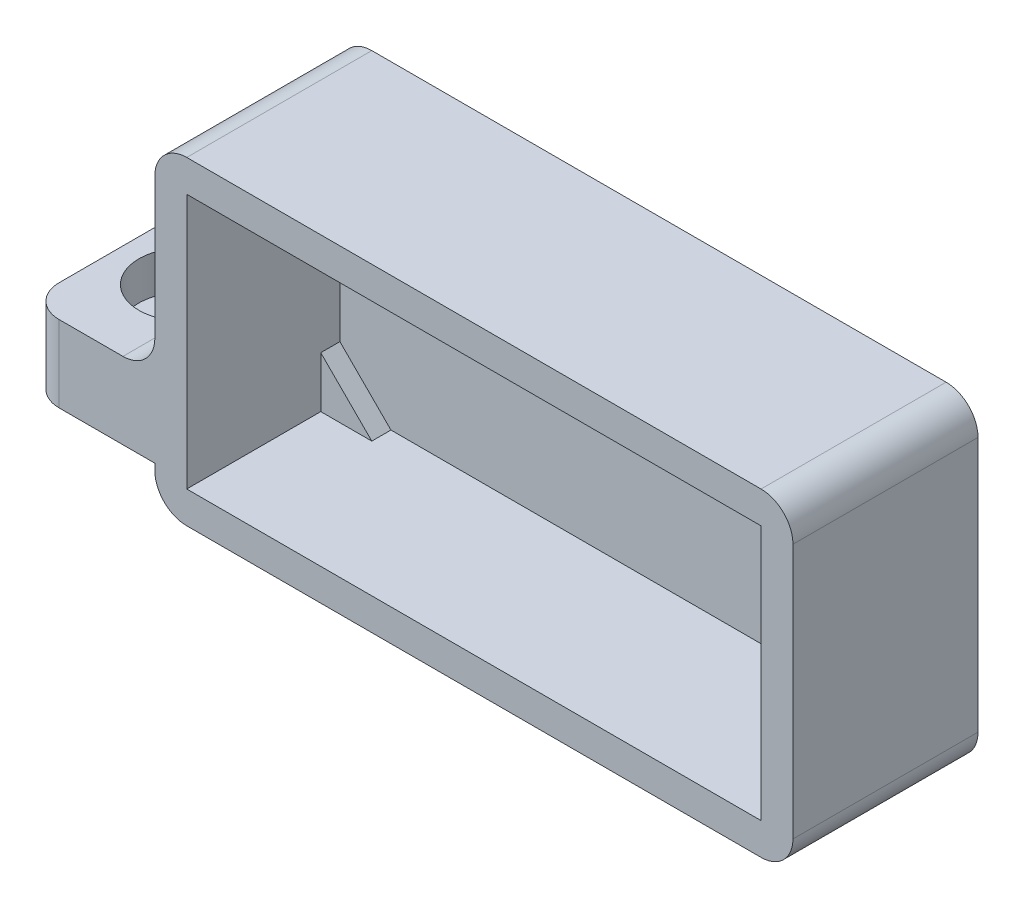
SolidWorks part; units mm, degrees
ref_plane "Front Plane" through (0, 0, 0) normal (0, 0, 1) x (1, 0, 0)
ref_plane "Top Plane" through (0, 0, 0) normal (0, 1, 0) x (1, 0, 0)
ref_plane "Right Plane" through (0, 0, 0) normal (1, 0, 0) x (0, 0, -1)
sketch "Sketch1" plane through (0, 0, 0) normal (0, 0, 1) x (1, 0, 0)
  line L1 (-25, 12.5) -> (25, 12.5)
  line L2 (-25, 12.5) -> (-25, -12.5)
  line L3 (-25, -12.5) -> (25, -12.5)
  line L4 (25, 12.5) -> (25, -12.5)
  line L5 (-25, 12.5) -> (25, -12.5) construction
  line L6 (-25, -12.5) -> (25, 12.5) construction
  point P0 (0, 0)
  dimension "D1" = 25
  dimension "D2" = 50
extrude "Boss-Extrude1" add sketch "Sketch1" along normal blind 2.5
sketch "Sketch2" plane through (0, 0, 2.5) normal (0, 0, 1) x (1, 0, 0)
  line L0 (25, 12.5) -> (-25, 12.5) construction
  line L1 (-22.5, 10) -> (22.5, 10)
  line L2 (-22.5, 10) -> (-22.5, -10)
  line L3 (-22.5, -10) -> (22.5, -10)
  line L4 (22.5, 10) -> (22.5, -10)
  line L5 (-22.5, 10) -> (22.5, -10) construction
  line L6 (-22.5, -10) -> (22.5, 10) construction
  line L7 (-25, 12.5) -> (-25, -12.5) construction
  line L9 (25, 12.5) -> (-25, 12.5)
  line L10 (25, 12.5) -> (25, -12.5)
  line L11 (25, -12.5) -> (-25, -12.5)
  line L12 (-25, 12.5) -> (-25, -12.5)
  line L13 (25, 12.5) -> (-25, -12.5) construction
  line L14 (25, -12.5) -> (-25, 12.5) construction
  point P0 (0, 0)
  point P10 (0, 0)
  dimension "D1" = 2.5
  dimension "D2" = 2.5
extrude "Boss-Extrude2" add sketch "Sketch2" along normal blind 12
sketch "Sketch4" plane through (0, 0, 2.5) normal (0, 0, 1) x (1, 0, 0)
  line L0 (0, 10) -> (0, -10) construction
  line L1 (22.5, 10) -> (-22.5, 10) construction
  line L2 (-22.5, -10) -> (22.5, -10) construction
  line L3 (-22.5, 0) -> (22.5, 0) construction
  line L4 (-22.5, 10) -> (-22.5, -10) construction
  line L5 (22.5, -10) -> (22.5, 10) construction
  line L6 (-22.5, 10) -> (-22.5, 6)
  line L7 (-22.5, 6) -> (-18.5, 10)
  line L8 (22.5, 10) -> (-22.5, 10) construction
  line L9 (-18.5, 10) -> (-22.5, 10)
  line L10 (18.5, 10) -> (22.5, 10)
  line L11 (22.5, 6) -> (18.5, 10)
  line L12 (22.5, 10) -> (22.5, 6)
  line L13 (22.5, -10) -> (22.5, -6)
  line L14 (22.5, -6) -> (18.5, -10)
  line L15 (18.5, -10) -> (22.5, -10)
  line L16 (-18.5, -10) -> (-22.5, -10)
  line L17 (-22.5, -6) -> (-18.5, -10)
  line L18 (-22.5, -10) -> (-22.5, -6)
  dimension "D1" = 4
extrude "Boss-Extrude3" add sketch "Sketch4" along normal blind 1.5
sketch "Sketch5" plane through (-25, 0, 0) normal (-1, 0, 0) x (0, 0, 1)
  line L0 (0, 12.5) -> (0, -12.5) construction
  line L1 (0, -3.5) -> (14.5, -3.5)
  line L2 (0, -3.5) -> (0, -9.5)
  line L3 (0, -9.5) -> (14.5, -9.5)
  line L4 (14.5, -3.5) -> (14.5, -9.5)
  line L5 (14.5, 12.5) -> (14.5, -12.5) construction
  line L6 (14.5, -12.5) -> (0, -12.5) construction
  dimension "D1" = 3
  dimension "D2" = 6
extrude "Boss-Extrude4" add sketch "Sketch5" along normal blind 10
sketch "Sketch6" plane through (0, -3.5, 0) normal (0, 1, 0) x (1, 0, 0)
  line L0 (-35, 0) -> (-25, 0) construction
  line L1 (-35, -14.5) -> (-35, 0) construction
  circle A0 centre (-30, -7.25) radius 1.6
  point P4 (-30, 0)
  point P7 (-35, -7.25)
  dimension "D1" = 3.2
extrude "Cut-Extrude1" cut sketch "Sketch6" against normal through all
sketch "Sketch7" plane through (0, -3.5, 0) normal (0, 1, 0) x (1, 0, 0)
  circle A0 centre (-30, -7.25) radius 3.5
  dimension "D1" = 7
extrude "Cut-Extrude2" cut sketch "Sketch7" against normal blind 3
fillet "Fillet1" radius 2.5 7 edges at (-25, -12.5, 7.25) (25, -12.5, 7.25) (25, 12.5, 7.25) (-25, 12.5, 7.25) (-35, -6.5, 0) (-35, -6.5, 14.5)
sketch "Sketch8" [suppressed] plane through (15, 0, 0) normal (1, 0, 0) x (0, 0, -1)
  line L0 (-14.5, -12.5) -> (-14.5, 12.5) construction
  line L1 (-14.5, -3.5) -> (0, -3.5)
  line L2 (-14.5, -3.5) -> (-14.5, -9.5)
  line L3 (-14.5, -9.5) -> (0, -9.5)
  line L4 (0, -3.5) -> (0, -9.5)
  line L5 (0, -12.5) -> (0, 12.5) construction
  line L6 (-14.5, -12.5) -> (0, -12.5) construction
  dimension "D1" = 3
  dimension "D2" = 6
extrude "Boss-Extrude5" [suppressed] add sketch "Sketch8" along normal blind 10
sketch "Sketch9" [suppressed] plane through (0, -3.5, 0) normal (0, 1, 0) x (1, 0, 0)
  line L0 (25, 0) -> (15, 0) construction
  line L1 (25, 0) -> (25, -14.5) construction
  circle A0 centre (20, -7.25) radius 1.6
  point P4 (20, 0)
  point P7 (25, -7.25)
  dimension "D1" = 3.2
extrude "Cut-Extrude3" [suppressed] cut sketch "Sketch9" against normal through all
sketch "Sketch10" [suppressed] plane through (0, -3.5, 0) normal (0, 1, 0) x (1, 0, 0)
  circle A0 centre (20, -7.25) radius 3.5
  dimension "D1" = 7
extrude "Cut-Extrude4" [suppressed] cut sketch "Sketch10" against normal blind 3
fillet "Fillet2" [suppressed] radius 2.5
